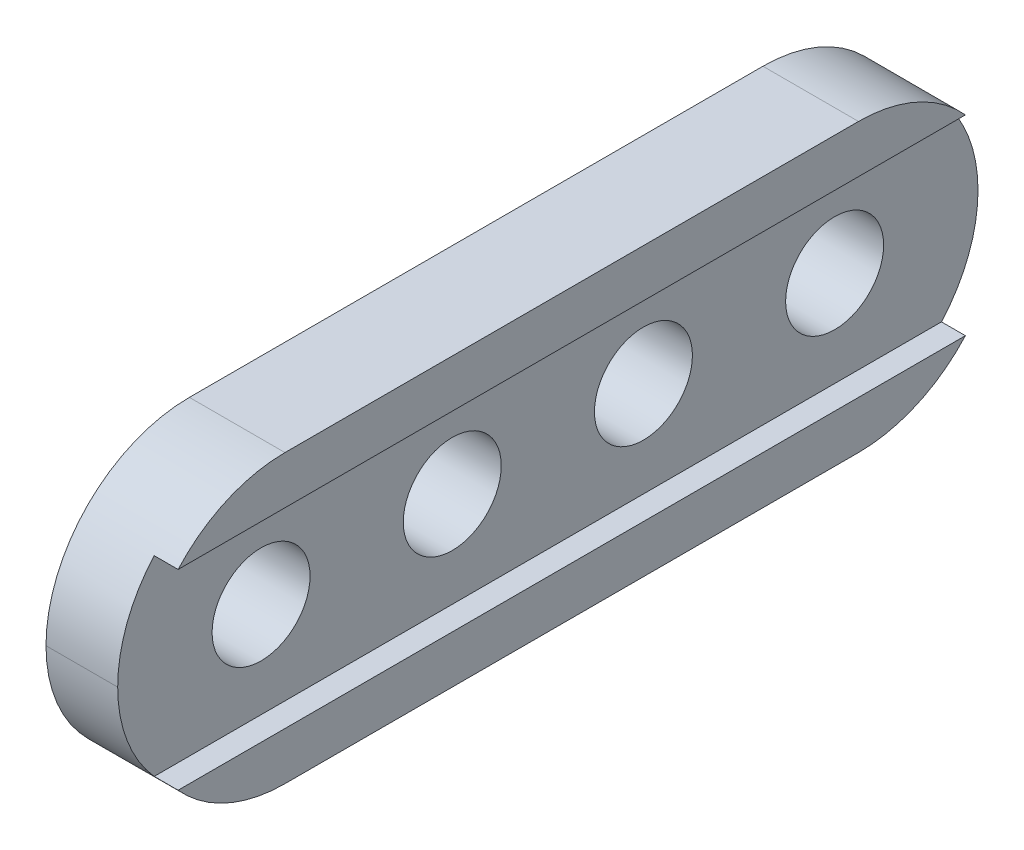
SolidWorks part; units mm, degrees
ref_plane "Front Plane" through (0, 0, 0) normal (0, 0, 1) x (1, 0, 0)
ref_plane "Top Plane" through (0, 0, 0) normal (0, 1, 0) x (1, 0, 0)
ref_plane "Right Plane" through (0, 0, 0) normal (1, 0, 0) x (0, 0, -1)
sketch "Sketch1" plane through (0, 0, 0) normal (0, 0, 1) x (1, 0, 0)
  line L0 (3, 6) -> (0, 6) construction
  line L1 (0, 0) -> (4, 0)
  line L2 (0, 0) -> (0, 12)
  line L3 (0, 12) -> (4, 12)
  line L4 (4, 0) -> (4, 2)
  line L5 (4, 10) -> (3, 10)
  line L7 (4, 2) -> (3, 2)
  line L8 (3, 10) -> (3, 2)
  line L9 (4, 10) -> (4, 12)
  dimension "D1" = 4
  dimension "D2" = 12
  dimension "D3" = 8
  dimension "D4" = 1
extrude "Boss-Extrude1" add sketch "Sketch1" against normal blind 36
ref_plane "Plane1" through (0, 0, -18) normal (0, 0, 1) x (1, 0, 0)
fillet "Fillet1" radius 6 4 edges at (2, 12, 0) (2, 0, 0) (2, 0, -36) (2, 12, -36)
sketch "Sketch2" plane through (0, 0, 0) normal (-1, 0, 0) x (0, 0, 1)
  circle A0 centre (-30, 6) radius 2.05
  dimension "D1" = 4.1
extrude "Cut-Extrude1" cut sketch "Sketch2" against normal through all
pattern_linear "LPattern1" count 2 spacing 8 along (0, 0, 1) of "Cut-Extrude1"
mirror "Mirror1" about plane through (0, 0, -18) normal (0, 0, 1) of "LPattern1", "Cut-Extrude1"
